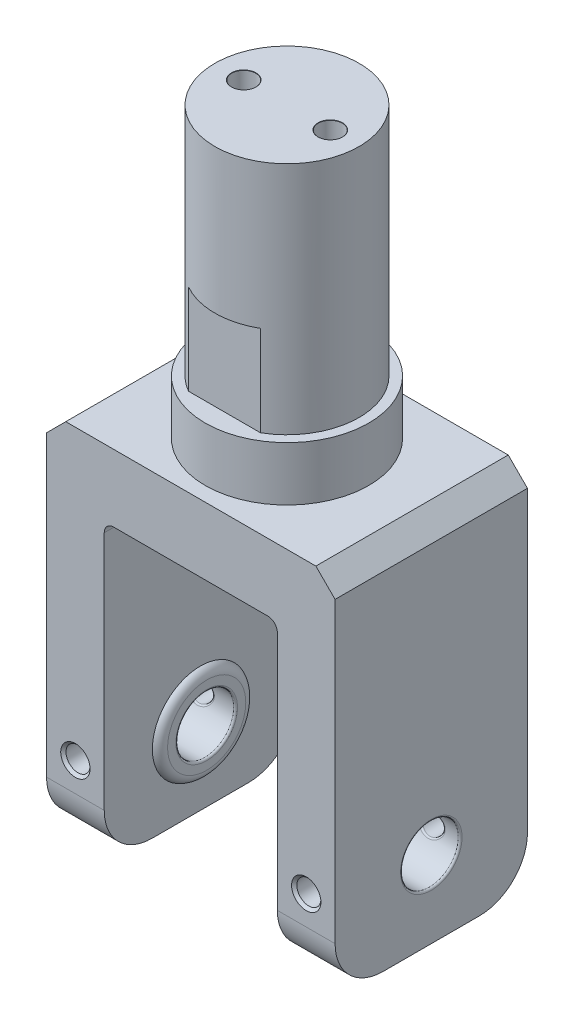
SolidWorks part; units mm, degrees
ref_plane "前视基准面" through (0, 0, 0) normal (0, 0, 1) x (1, 0, 0)
ref_plane "上视基准面" through (0, 0, 0) normal (0, 1, 0) x (1, 0, 0)
ref_plane "右视基准面" through (0, 0, 0) normal (1, 0, 0) x (0, 0, -1)
other "Configuration Table"
sketch "草图1" plane through (0, 0, 0) normal (0, 1, 0) x (1, 0, 0)
  line L1 (-15, -10) -> (15, -10)
  line L2 (-15, -10) -> (-15, 10)
  line L3 (-15, 10) -> (15, 10)
  line L4 (15, -10) -> (15, 10)
  line L5 (0, 10) -> (0, -10) construction
  line L6 (-15, 0) -> (15, 0) construction
  point P0 (0, 0)
  dimension "D1" = 30
  dimension "D2" = 20
extrude "凸台-拉伸1" add sketch "草图1" along normal blind 40
sketch "草图2" plane through (0, 0, 10) normal (0, 0, 1) x (1, 0, 0)
  line L0 (15, 40) -> (15, 0) construction
  line L1 (-9, 33) -> (9, 33)
  line L2 (-9, 33) -> (-9, -1)
  line L3 (-9, -1) -> (9, -1)
  line L4 (9, 33) -> (9, -1)
  line L5 (-15, 40) -> (-15, 0) construction
  line L6 (-15, 40) -> (15, 40) construction
  dimension "D1" = 6
  dimension "D2" = 6
  dimension "D3" = 7
  dimension "D4" = 34
extrude "切除-拉伸1" cut sketch "草图2" against normal through all
sketch "草图3" plane through (15, 0, 0) normal (1, 0, 0) x (0, 0, -1)
  line L0 (-10, 40) -> (10, 40) construction
  circle A0 centre (0, 10) radius 3
  dimension "D2" = 6
  dimension "D1" = 30
extrude "切除-拉伸2" cut sketch "草图3" against normal through all
chamfer "倒角1" distance 2 angle 45 2 edges at (-15, 40, 0) (15, 40, 0)
chamfer "倒角2" distance 1 angle 45 4 edges at (15, 0, 0) (9, 0, 0) (-9, 0, 0) (-15, 0, 0)
fillet "圆角1" radius 1 2 edges at (9, 33, 0) (-9, 33, 0)
sketch "草图4" plane through (-9, 0, 0) normal (1, 0, 0) x (0, 0, -1)
  circle A0 centre (0, 10) radius 5
  circle A1 centre (0, 10) radius 3
  dimension "D1" = 10
  dimension "D2" = 6
extrude "凸台-拉伸2" add sketch "草图4" along normal blind 0.65
fillet "圆角2" radius 1 1 edges at (-8.35, 15, 0)
mirror "镜向1" about plane through (0, 0, 0) normal (1, 0, 0) of "凸台-拉伸2", "圆角2"
sketch "草图5" plane through (0, 40, 0) normal (0, 1, 0) x (1, 0, 0)
  circle A0 centre (0, 0) radius 8.5
  dimension "D1" = 17
extrude "凸台-拉伸3" add sketch "草图5" along normal blind 5.62
sketch "草图6" plane through (0, 45.62, 0) normal (0, 1, 0) x (1, 0, 0)
  circle A0 centre (0, 0) radius 7.5
  dimension "D1" = 15
extrude "凸台-拉伸4" add sketch "草图6" along normal blind 24.4
hole_wizard "M3 螺纹孔1" positions "草图7" profile "草图8" tap size "M3" standard "GB" end condition through all
sketch "草图7" plane through (0, 0, 10) normal (0, 0, 1) x (1, 0, 0)
  line L0 (-9, 32) -> (-9, 1) construction
  line L1 (9, 15) -> (9, 5) construction
  line L2 (-13, 40) -> (13, 40) construction
  point P0 (-12, 10)
  point P2 (12, 10)
  dimension "D1" = 3
  dimension "D2" = 3
  dimension "D3" = 30
sketch "草图8" plane through (-12, 10, 10) normal (1, 0, 0) x (0, -1, 0)
  line L0 (0, 0) -> (0, 20)
  line L1 (0, 20) -> (1.25, 20)
  line L2 (1.25, 20) -> (1.25, 0.275)
  line L3 (1.25, 0.275) -> (1.525, 0)
  line L5 (1.525, 0) -> (0, 0)
  line L6 (-1.25, 0.275) -> (-1.525, 0) construction
  line L11 (0, -6.35) -> (0, 107.95) construction
  dimension "通孔螺纹孔钻头直径" = 2.5
  dimension "通孔螺纹孔钻头深度" = 20
  dimension "近端锥形沉头孔直径" = 3.05
  dimension "近端锥形沉头孔角度" = 90
cosmetic thread "孔螺蚊线1" parameters "D2"=3
cosmetic thread "孔螺蚊线2" parameters "D2"=3
hole_wizard "Ø2.5mm 暗销孔1" positions "3D草图4" profile "草图12" hole size "Ø2.5" standard "GB"
sketch3d "3D草图4"
  line L1 (0, 70.02, 0) -> (2.4638, 70.02, 0) construction
  line L2 (0, 70.02, 0) -> (0, 45.62, 0) construction
  point P0 (4.5, 70.02, 0)
  point P2 (-4.5, 70.02, 0)
  dimension "D1" = 4.5
  dimension "D2" = 4.5
sketch "草图12" plane through (4.5, 70.02, 0) normal (1, 0, 0) x (0, 0, 1)
  line L0 (0, 0) -> (0, 9.2511)
  line L1 (0, 9.2511) -> (1.25, 8.5)
  line L2 (1.25, 8.5) -> (1.25, 0.025)
  line L3 (1.25, 0.025) -> (1.275, 0)
  line L5 (1.275, 0) -> (0, 0)
  line L6 (-1.25, 0.025) -> (-1.275, 0) construction
  line L10 (0, 9.2511) -> (-1.25, 8.5) construction
  line L11 (0, -6.35) -> (0, 107.95) construction
  dimension "孔直径" = 2.5
  dimension "孔深度" = 8.5
  dimension "近端锥形沉头孔直径" = 2.55
  dimension "近端锥形沉头孔角度" = 90
  dimension "导头角度" = 118
fillet "圆角3" radius 0.2 8 edges at (15, 10, -3) (-15, 10, -3) (-8.35, 13, 0) (8.35, 13, 0) (13.238, 9.8273, -2.995) (10.762, 9.8273, 2.995) (-10.762, 9.8273, -2.995) (-13.238, 9.8273, 2.995)
sketch "草图13" plane through (0, 70.02, 0) normal (0, 1, 0) x (1, 0, 0)
  line L1 (-6.5, 5.6395) -> (-8.3592, 5.6395)
  line L2 (-6.5, 5.6395) -> (-6.5, -5.4884)
  line L3 (-6.5, -5.4884) -> (-8.3592, -5.4884)
  line L4 (-8.3592, 5.6395) -> (-8.3592, -5.4884)
  line L5 (6.8797, -6.5) -> (-6.1306, -6.5)
  line L6 (6.8797, -6.5) -> (6.8797, -12.2569)
  line L7 (6.8797, -12.2569) -> (-6.1306, -12.2569)
  line L8 (-6.1306, -6.5) -> (-6.1306, -12.2569)
  circle A1 centre (0, 0) radius 7.5 construction
  circle A2 centre (0, 0) radius 10 construction
  circle A3 centre (0, 0) radius 7.5
  circle M9 centre (-4.5, 0) radius 1.275
  circle M10 centre (0, 0) radius 7.5
  dimension "D2" = 1
  dimension "D1" = 1
extrude "切除-拉伸3" cut sketch "草图13" against normal up to surface (24.4 mm away) from offset 15 contours L2 M10 M9 | L5 M10 region at (-6.9024, 70.02, 0) region at (0, 70.02, 6.9024) up to face at (0, 45.62, 7.5) offset against normal yes
sketch "草图14" plane through (0, 0, -10) normal (0, 0, -1) x (-1, 0, 0)
  line L0 (10, 0) -> (14, 0) construction
  line L1 (-22.1259, 2) -> (24.9312, 2)
  line L2 (-22.1259, 2) -> (-22.1259, -5)
  line L3 (-22.1259, -5) -> (24.9312, -5)
  line L4 (24.9312, 2) -> (24.9312, -5)
  dimension "D1" = 2
  dimension "D2" = 7
  dimension "D3" = 47.0571
extrude "切除-拉伸4" cut sketch "草图14" against normal through all
fillet "圆角5" radius 5 4 edges at (12, 2, 10) (-12, 2, -10) (-12, 2, 10) (12, 2, -10)
